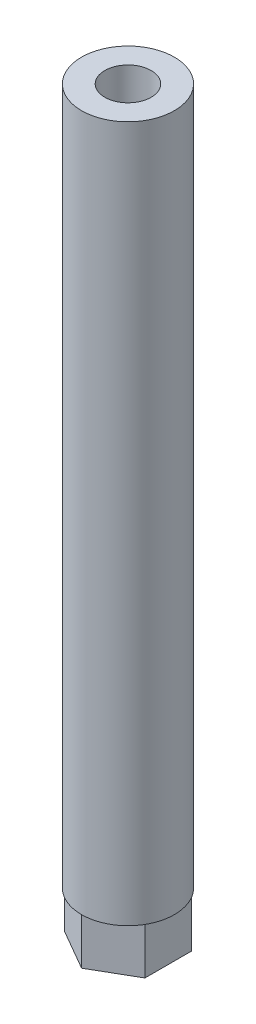
SolidWorks part; units mm, degrees
ref_plane "Alzado" through (0, 0, 0) normal (0, 0, 1) x (1, 0, 0)
ref_plane "Planta" through (0, 0, 0) normal (0, 1, 0) x (1, 0, 0)
ref_plane "Vista lateral" through (0, 0, 0) normal (1, 0, 0) x (0, 0, -1)
sketch "Croquis1" plane through (0, 0, 0) normal (0, 1, 0) x (1, 0, 0)
  circle A0 centre (0, 0) radius 10
  dimension "D1" = 20
extrude "Saliente-Extruir1" add sketch "Croquis1" along normal blind 150
sketch "Croquis2" plane through (0, 0, 0) normal (0, -1, 0) x (1, 0, 0)
  line L54 (0, 9.9882) -> (-8.65, 4.9941)
  line L55 (-8.65, 4.9941) -> (-8.65, -4.9941)
  line L56 (-8.65, -4.9941) -> (0, -9.9882)
  line L57 (0, -9.9882) -> (8.65, -4.9941)
  line L58 (8.65, -4.9941) -> (8.65, 4.9941)
  line L59 (8.65, 4.9941) -> (0, 9.9882)
  circle A1 centre (0, 0) radius 8.65 construction
  circle A5 centre (0, 0) radius 1.75
  point P13 (0, 0)
  point P62 (0, 0)
  dimension "D1" = 17.3
extrude "Saliente-Extruir2" add sketch "Croquis2" along normal blind 10 contours A5 | L54 L55 L56 L57 L58 L59
sketch "Croquis5" plane through (0, 150, 0) normal (0, -1, 0) x (1, 0, 0)
  circle A0 centre (0, 0) radius 5
  dimension "D1" = 10
extrude "Cortar-Extruir1" cut sketch "Croquis5" against normal through all both and the other way through all
sketch "Croquis7" plane through (0, -10, 0) normal (0, -1, 0) x (1, 0, 0)
  circle A0 centre (0, 0) radius 1.75
  circle A1 centre (0, 0) radius 5
  dimension "D1" = 10
  dimension "D2" = 3.5
extrude "Saliente-Extruir4" add sketch "Croquis7" against normal blind 30
